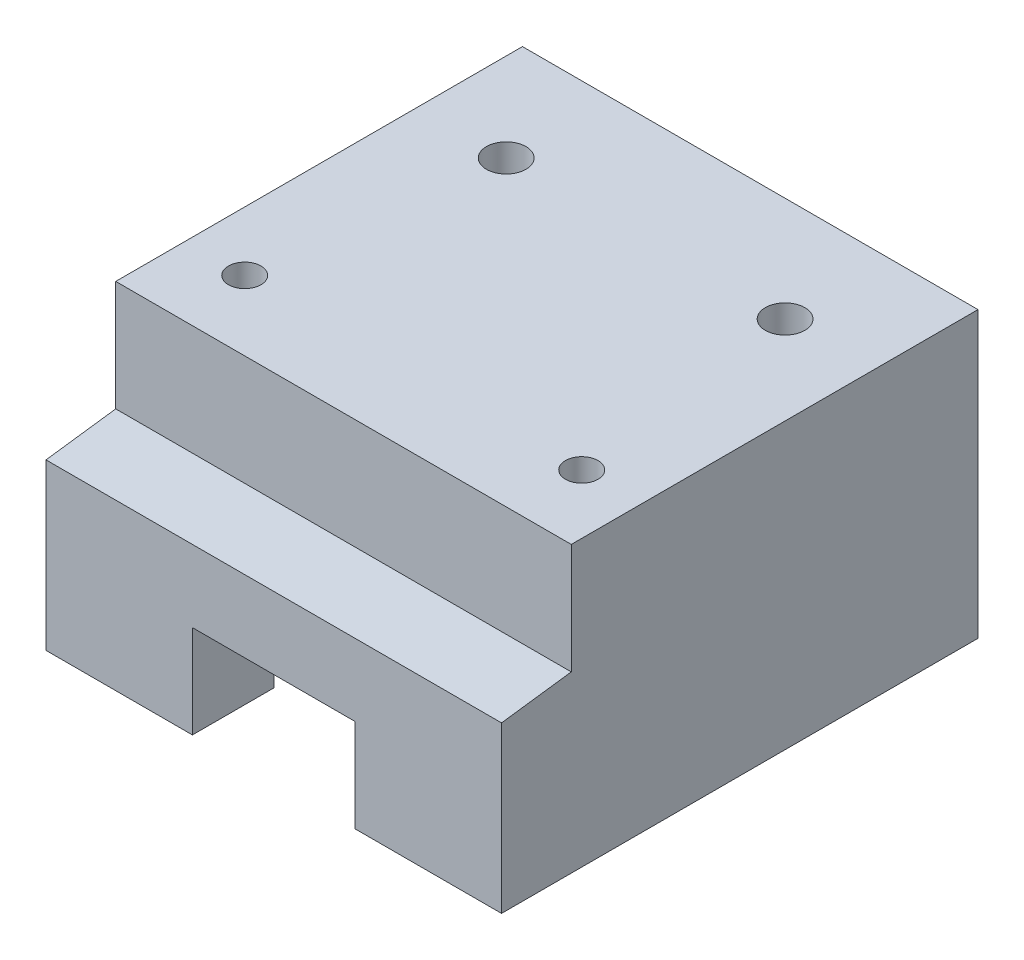
SolidWorks part; units mm, degrees
ref_plane "Спереди" through (0, 0, 0) normal (0, 0, 1) x (1, 0, 0)
ref_plane "Сверху" through (0, 0, 0) normal (0, 1, 0) x (1, 0, 0)
ref_plane "Справа" through (0, 0, 0) normal (1, 0, 0) x (0, 0, -1)
sketch "Эскиз1" plane through (0, 0, 0) normal (0, 0, 1) x (1, 0, 0)
  line L1 (20, -10) -> (-20, -10)
  line L2 (20, -10) -> (20, 10)
  line L3 (20, 10) -> (-20, 10)
  line L4 (-20, -10) -> (-20, 10)
  line L5 (20, -10) -> (-20, 10) construction
  line L6 (20, 10) -> (-20, -10) construction
  point P0 (0, 0)
  dimension "D1" = 40
  dimension "D2" = 20
extrude "Бобышка-Вытянуть1" add sketch "Эскиз1" along normal blind 6
sketch "Эскиз2" plane through (0, 0, 0) normal (0, 0, -1) x (-1, 0, 0)
  line L0 (20, -10) -> (-20, -10) construction
  line L1 (20, 22.5) -> (-20, 22.5)
  line L2 (20, 22.5) -> (20, -10)
  line L3 (20, -10) -> (-20, -10)
  line L4 (-20, 22.5) -> (-20, -10)
  line L5 (20, 22.5) -> (-20, -10) construction
  line L6 (20, -10) -> (-20, 22.5) construction
  line L7 (-20, -10) -> (-20, 10) construction
  point P0 (0, 6.25)
  dimension "D1" = 22.5
extrude "Бобышка-Вытянуть2" add sketch "Эскиз2" along normal blind 35
sketch "Эскиз3" plane through (0, -10, 0) normal (0, -1, 0) x (1, 0, 0)
  line L0 (0, 6) -> (0, -35) construction
  line L1 (-20, 6) -> (20, 6) construction
  line L2 (20, -35) -> (-20, -35) construction
  line L3 (-7, 6) -> (-7, -1)
  line L4 (-7, -1) -> (-9, -1)
  line L5 (-9, -1) -> (-9, -23)
  line L6 (-9, -23) -> (-6.5, -26)
  line L7 (-6.5, -26) -> (-6.5, -33)
  line L8 (-6.5, -33) -> (-4.5, -33)
  line L9 (-4.5, -33) -> (-4.5, -35)
  line L10 (4.5, -33) -> (4.5, -35)
  line L11 (6.5, -33) -> (4.5, -33)
  line L12 (6.5, -26) -> (6.5, -33)
  line L13 (9, -23) -> (6.5, -26)
  line L14 (9, -1) -> (9, -23)
  line L15 (7, -1) -> (9, -1)
  line L16 (7, 6) -> (7, -1)
  line L17 (-7, 6) -> (7, 6)
  line L18 (4.5, -35) -> (-4.5, -35)
  dimension "D1" = 7
  dimension "D2" = 9
  dimension "D3" = 6.5
  dimension "D4" = 4.5
  dimension "D5" = 7
  dimension "D6" = 22
  dimension "D7" = 32
  dimension "D8" = 25
extrude "Вырез-Вытянуть1" cut sketch "Эскиз3" against normal blind 13
sketch "Эскиз5" plane through (0, 3, 0) normal (0, -1, 0) x (1, 0, 0)
  line L0 (-9, -1) -> (9, -1)
  line L1 (9, -1) -> (9, -23)
  line L2 (9, -23) -> (6.5, -26)
  line L3 (6.5, -26) -> (6.5, -33)
  line L4 (6.5, -33) -> (-6.5, -33)
  line L5 (-6.5, -33) -> (-6.5, -26)
  line L6 (-6.5, -26) -> (-9, -23)
  line L7 (-9, -23) -> (-9, -1)
extrude "Вырез-Вытянуть2" cut sketch "Эскиз5" against normal blind 2
sketch "Эскиз6" plane through (0, -10, 0) normal (0, -1, 0) x (1, 0, 0)
  line L0 (20, 6) -> (20, -35) construction
  line L1 (-20, -35) -> (20, -35)
  line L2 (-20, -35) -> (-20, 6)
  line L3 (-20, 6) -> (20, 6)
  line L4 (20, -35) -> (20, 6)
  line L6 (-20, 6) -> (-7, 6) construction
extrude "Вырез-Вытянуть3" cut sketch "Эскиз6" against normal blind 5
sketch "Эскиз8" plane through (0, -5, 0) normal (0, -1, 0) x (1, 0, 0)
  line L0 (0, 6) -> (0, -35) construction
  line L1 (7, 6) -> (-7, 6) construction
  line L2 (-4.5, -35) -> (4.5, -35) construction
  line L3 (9, -6) -> (20, -6) construction
  line L4 (9, -23) -> (9, -1) construction
  line L5 (20, -35) -> (20, 6) construction
  line L6 (20, 6) -> (7, 6) construction
  circle A0 centre (12, -26) radius 1.7
  circle A1 centre (14.5, -6) radius 1.4
  circle A2 centre (-12, -26) radius 1.7
  circle A3 centre (-14.5, -6) radius 1.4
  dimension "D1" = 12
  dimension "D2" = 3.4
  dimension "D4" = 2.8
  dimension "D3" = 12
extrude "Вырез-Вытянуть4" cut sketch "Эскиз8" against normal through all
sketch "Эскиз9" plane through (0, 0, 0) normal (0, 0, 1) x (1, 0, 0)
  line L2 (20, 22.5) -> (20, 10) construction
  line L3 (-20, 22.5) -> (20, 22.5)
  line L4 (-20, 22.5) -> (-20, 19.5)
  line L5 (-20, 19.5) -> (20, 19.5)
  line L6 (20, 22.5) -> (20, 19.5)
  dimension "D1" = 3
extrude "Вырез-Вытянуть5" cut sketch "Эскиз9" against normal up to surface (35 mm away) up to face at (0, 3.875, -35)
chamfer "Фаска1" distance 6 distance2 0.8 1 edges at (0, 10, 6) first distance on face at (0, 10, 3)
sketch "Эскиз11" plane through (0, 19.5, 0) normal (0, 1, 0) x (1, 0, 0)
  line L0 (20, 35) -> (-20, 35) construction
  line L1 (-19.6, 35) -> (-20, 35)
  line L2 (-19.6, 35) -> (-19.6, -6)
  line L3 (-19.6, -6) -> (-20, -6)
  line L4 (-20, 35) -> (-20, -6)
  line L5 (20, -6) -> (-20, -6) construction
  line L6 (-20, 35) -> (-20, 0) construction
  line L7 (0, 35) -> (0, -6) construction
  line L8 (20, 35) -> (20, -6)
  line L9 (19.6, -6) -> (20, -6)
  line L10 (19.6, 35) -> (19.6, -6)
  line L11 (19.6, 35) -> (20, 35)
  dimension "D1" = 0.4
extrude "Вырез-Вытянуть6" cut sketch "Эскиз11" against normal up to surface (24.5 mm away) up to face at (15.9, -5, -6)
